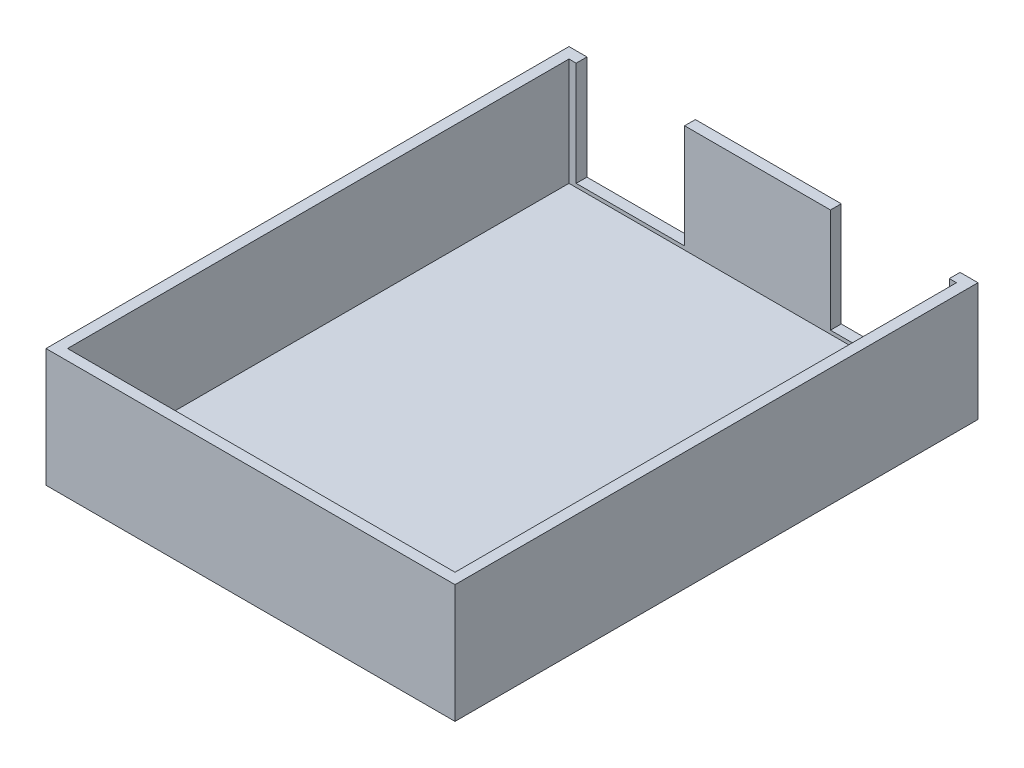
SolidWorks part; units mm, degrees
ref_plane "Front" through (0, 0, 0) normal (0, 0, 1) x (1, 0, 0)
ref_plane "Top" through (0, 0, 0) normal (0, 1, 0) x (1, 0, 0)
ref_plane "Right" through (0, 0, 0) normal (1, 0, 0) x (0, 0, -1)
sketch "Sketch1" plane through (0, 0, 0) normal (0, 1, 0) x (1, 0, 0)
  line L0 (-19.6957, 22.2835) -> (34.2793, 22.2835)
  line L1 (-21.1957, 23.7835) -> (35.7793, 23.7835)
  line L2 (-21.1957, 23.7835) -> (-21.1957, -49.0665)
  line L3 (-21.1957, -49.0665) -> (35.7793, -49.0665)
  line L4 (35.7793, 23.7835) -> (35.7793, -49.0665)
  line L5 (34.2793, 22.2835) -> (34.2793, -47.5665)
  line L6 (-19.6957, -47.5665) -> (34.2793, -47.5665)
  line L7 (-19.6957, 22.2835) -> (-19.6957, -47.5665)
  dimension "D1" = 56.975
  dimension "D2" = 72.85
  dimension "D3" = 1.5
extrude "Boss-Extrude1" add sketch "Sketch1" along normal blind 1.5 contours L0 L5 L6 L7
extrude "Boss-Extrude2" add sketch "Sketch1<4>" along normal blind 16.5
sketch "Sketch1<4>" plane through (0, 0, 0) normal (0, 1, 0) x (1, 0, 0) same geometry as "Sketch1"
sketch "Sketch2" plane through (0, 0, -23.7835) normal (0, 0, -1) x (-1, 0, 0)
  line L0 (-35.7793, 0) -> (21.1957, 0) construction
  line L1 (-35.7793, 16.5) -> (-16.7293, 16.5)
  line L2 (-35.7793, 16.5) -> (-35.7793, 0)
  line L3 (-35.7793, 0) -> (-16.7293, 0)
  line L4 (-16.7293, 16.5) -> (-16.7293, 0)
  line L5 (-33.2793, 16.5) -> (-33.2793, 0)
  line L6 (21.1957, 16.5) -> (3.5907, 16.5)
  line L7 (21.1957, 16.5) -> (21.1957, 0)
  line L8 (21.1957, 0) -> (3.5907, 0)
  line L9 (3.5907, 16.5) -> (3.5907, 0)
  line L10 (18.6957, 16.5) -> (18.6957, 0)
  line L11 (-33.2793, 2) -> (18.6957, 2)
  point P19 (18.6957, 2)
  line M12 (21.1957, 16.5) -> (-35.7793, 16.5)
  dimension "D1" = 20.32
  dimension "D2" = 39.37
  dimension "D3" = 2.5
  dimension "D4" = 2
  dimension "D5" = 2.5
extrude "Cut-Extrude1" cut sketch "Sketch2" against normal up to next contours L5 L11 L4 M12 | L9 L11 L10 L6 region at (25.0043, 9.25, -23.7835) region at (-11.1432, 9.25, -23.7835)
